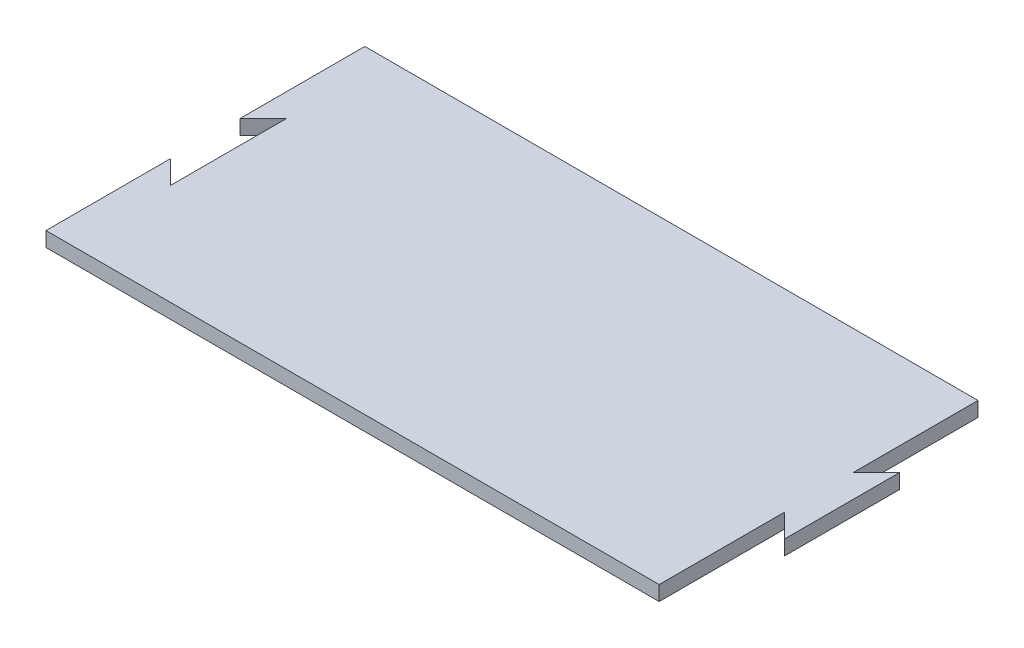
SolidWorks part; units mm, degrees
ref_plane "Front Plane" through (0, 0, 0) normal (0, 0, 1) x (1, 0, 0)
ref_plane "Top Plane" through (0, 0, 0) normal (0, 1, 0) x (1, 0, 0)
ref_plane "Right Plane" through (0, 0, 0) normal (1, 0, 0) x (0, 0, -1)
other "Default"
sketch "Sketch1" plane through (0, 0, 0) normal (0, 1, 0) x (1, 0, 0)
  line L0 (-354.15, 75) -> (-354.15, -75)
  line L1 (-354.15, -75) -> (-260.5, -75)
  line L2 (-260.5, -75) -> (-260.5, -68.65)
  line L3 (-260.5, -68.65) -> (260.5, -68.65)
  line L4 (260.5, -68.65) -> (260.5, -75)
  line L5 (260.5, -75) -> (354.15, -75)
  line L6 (354.15, -75) -> (354.15, 75)
  line L7 (354.15, 75) -> (260.5, 75)
  line L8 (260.5, 75) -> (260.5, 68.65)
  line L9 (260.5, 68.65) -> (-260.5, 68.65)
  line L10 (-260.5, 68.65) -> (-260.5, 75)
  line L11 (-260.5, 75) -> (-354.15, 75)
  point P11 (0, -68.65)
  point P13 (354.15, 0)
  dimension "D1" = 150
  dimension "D2" = 6.35
  dimension "TabWidth" = 93.65
  dimension "Width" = 708.3
extrude "Boss-Extrude1" add sketch "Sketch1" along normal mid plane 6.35
sketch "Sketch2" [suppressed] plane through (0, 3.175, 0) normal (0, 1, 0) x (1, 0, 0)
  line L0 (233.15, -86.7757) -> (233.15, 92.4765) construction
  line L5 (239.5, 75) -> (139.5, 75) construction
  line L6 (43.15, -11.35) -> (183.15, -11.35)
  line L7 (188.15, 88.359) -> (188.15, -110.3451) construction
  line L8 (-49.46, 51.57) -> (-49.46, 61.57) construction
  line L13 (239.5, -75) -> (239.5, 75) construction
  line L14 (38.15, -90.5492) -> (38.15, 114.8099) construction
  line L23 (139.5, 68.65) -> (-139.5, 68.65) construction
  line L24 (-80.91, -8.28) -> (18.15, -8.28) construction
  line L25 (-80.91, -8.28) -> (-80.91, 66.65) construction
  line L26 (-80.91, 66.65) -> (18.15, 66.65) construction
  line L27 (18.15, -8.28) -> (18.15, 66.65) construction
  line L28 (-80.91, -8.28) -> (18.15, 66.65) construction
  line L29 (-80.91, 66.65) -> (18.15, -8.28) construction
  line L30 (-75.83, -3.2) -> (13.07, -3.2) construction
  line L31 (-75.83, -3.2) -> (-75.83, 61.57) construction
  line L32 (-75.83, 61.57) -> (13.07, 61.57) construction
  line L33 (13.07, -3.2) -> (13.07, 61.57) construction
  line L34 (-75.83, -3.2) -> (13.07, 61.57) construction
  line L35 (-75.83, 61.57) -> (13.07, -3.2) construction
  line L36 (-155.36, 15.85) -> (-110.91, 15.85) construction
  line L37 (-155.36, 15.85) -> (-155.36, 66.65) construction
  line L38 (-155.36, 66.65) -> (-110.91, 66.65) construction
  line L39 (-110.91, 15.85) -> (-110.91, 66.65) construction
  line L40 (-155.36, 15.85) -> (-110.91, 66.65) construction
  line L41 (-155.36, 66.65) -> (-110.91, 15.85) construction
  line L42 (-151.55, 19.66) -> (-114.72, 19.66) construction
  line L43 (-151.55, 19.66) -> (-151.55, 62.84) construction
  line L44 (-151.55, 62.84) -> (-114.72, 62.84) construction
  line L45 (-114.72, 19.66) -> (-114.72, 62.84) construction
  line L46 (-151.55, 19.66) -> (-114.72, 62.84) construction
  line L47 (-151.55, 62.84) -> (-114.72, 19.66) construction
  line L48 (-51.46, 51.57) -> (-51.46, 61.57)
  line L49 (-47.46, 51.57) -> (-47.46, 61.57)
  line L50 (-9.46, 51.57) -> (-9.46, 61.57) construction
  line L51 (-11.46, 51.57) -> (-11.46, 61.57)
  line L52 (-7.46, 51.57) -> (-7.46, 61.57)
  line L53 (43.15, -11.35) -> (43.15, 63.65)
  line L54 (43.15, 63.65) -> (183.15, 63.65)
  line L55 (183.15, -11.35) -> (183.15, 63.65)
  line L56 (43.15, -11.35) -> (183.15, 63.65) construction
  line L57 (43.15, 63.65) -> (183.15, -11.35) construction
  line L58 (194.5, 75) -> (188.15, 75)
  line L59 (194.5, 75) -> (194.5, 55)
  line L60 (194.5, 55) -> (188.15, 55)
  line L61 (188.15, 75) -> (188.15, 55)
  line L62 (31.8, -31.35) -> (194.5, -31.35) construction
  line L63 (194.5, -37.7) -> (188.15, -37.7)
  line L64 (194.5, -37.7) -> (194.5, -17.7)
  line L65 (194.5, -17.7) -> (188.15, -17.7)
  line L66 (188.15, -37.7) -> (188.15, -17.7)
  line L67 (38.15, -37.7) -> (31.8, -37.7)
  line L68 (38.15, -37.7) -> (38.15, -17.7)
  line L69 (38.15, -17.7) -> (31.8, -17.7)
  line L70 (31.8, -37.7) -> (31.8, -17.7)
  line L71 (38.15, 55) -> (31.8, 55)
  line L72 (38.15, 55) -> (38.15, 75)
  line L73 (38.15, 75) -> (31.8, 75)
  line L74 (31.8, 55) -> (31.8, 75)
  line L76 (103.15, -31.35) -> (123.15, -31.35)
  line L77 (103.15, -31.35) -> (103.15, -37.7)
  line L78 (103.15, -37.7) -> (123.15, -37.7)
  line L79 (123.15, -31.35) -> (123.15, -37.7)
  circle A0 centre (-75.83, 61.57) radius 1.375
  circle A1 centre (13.07, 61.57) radius 1.375
  circle A2 centre (13.07, -3.2) radius 1.375
  circle A3 centre (-75.83, -3.2) radius 1.375
  circle A4 centre (-42.81, -3.2) radius 1.375
  circle A6 centre (-114.72, 19.66) radius 1.375
  circle A7 centre (-151.55, 19.66) radius 1.375
  circle A8 centre (-151.55, 62.84) radius 1.375
  circle A9 centre (-114.72, 63.48) radius 1.375
  arc A10 (-51.46, 51.57) -> (-47.46, 51.57) centre (-49.46, 51.57) ccw
  arc A11 (-47.46, 61.57) -> (-51.46, 61.57) centre (-49.46, 61.57) ccw
  arc A12 (-11.46, 51.57) -> (-7.46, 51.57) centre (-9.46, 51.57) ccw
  arc A13 (-7.46, 61.57) -> (-11.46, 61.57) centre (-9.46, 61.57) ccw
  point P0 (113.15, 26.15)
  point P28 (-31.38, 29.185)
  point P33 (-31.38, 29.185)
  point P44 (-133.135, 41.25)
  point P49 (-133.135, 41.25)
  point P60 (-49.46, 56.57)
  point P67 (-9.46, 56.57)
  point P85 (113.15, -31.35)
  dimension "D17" = 2.75
  dimension "D25" = 0.64
  dimension "D27" = 2
  dimension "D4" = 6.35
  dimension "D5" = 5
  dimension "D7" = 5
  dimension "D8" = 75
  dimension "D9" = 150
  dimension "D10" = 6.35
  dimension "D12" = 45
  dimension "D13" = 99.06
  dimension "D14" = 74.93
  dimension "D15" = 88.9
  dimension "D16" = 64.77
  dimension "D18" = 2
  dimension "D19" = 20
  dimension "D20" = 33.02
  dimension "D21" = 50.8
  dimension "D22" = 44.45
  dimension "D23" = 36.83
  dimension "D24" = 43.18
  dimension "D26" = 30
  dimension "D28" = 26.37
  dimension "D29" = 22.53
  dimension "D30" = 10
  dimension "D6" = 5
  dimension "D31" = 100
  dimension "D32" = 20
extrude "Back Only" [suppressed] cut sketch "Sketch2" against normal through all
sketch "Sketch3" [suppressed] plane through (0, 3.175, 0) normal (0, 1, 0) x (1, 0, 0)
  line L0 (-225.15, 9.65) -> (-200.15, 9.65) construction
  line L1 (-230.15, -0.35) -> (-195.15, -0.35) construction
  line L2 (-230.15, -0.35) -> (-230.15, 19.65) construction
  line L3 (-230.15, 19.65) -> (-195.15, 19.65) construction
  line L4 (-195.15, -0.35) -> (-195.15, 19.65) construction
  line L5 (-230.15, -0.35) -> (-195.15, 19.65) construction
  line L6 (-230.15, 19.65) -> (-195.15, -0.35) construction
  line L9 (-233.15, -93.1255) -> (-233.15, 99.5323) construction
  line L10 (-239.5, 75) -> (-239.5, -75) construction
  line L11 (139.5, 68.65) -> (38.15, 68.65) construction
  line L12 (0, -88.5309) -> (0, 117.3513) construction
  circle A1 centre (-200.15, 9.65) radius 2.5
  circle A2 centre (-225.15, 9.65) radius 2.5
  circle A3 centre (200.15, 9.65) radius 2.5
  circle A5 centre (225.15, 9.65) radius 2.5
  point P0 (-212.65, 9.65)
  dimension "D4" = 5
  dimension "D1" = 35
  dimension "D2" = 20
  dimension "D5" = 25
  dimension "D6" = 59
  dimension "D7" = 6.35
  dimension "D8" = 3
extrude "Front and Back" [suppressed] cut sketch "Sketch3" against normal through all
sketch "Sketch4" plane through (0, -3.175, 0) normal (0, -1, 0) x (1, 0, 0)
  line L0 (-329.1, -3.15) -> (-323.1, -3.15) construction
  line L1 (202.9, -3.15) -> (208.9, -3.15) construction
  line L2 (-329.1, -3.15) -> (-323.1, -3.15) construction
  line L3 (202.9, -3.15) -> (208.9, -3.15) construction
  line L4 (-184.15, -68.65) -> (-184.15, -15)
  line L5 (260.5, -68.65) -> (-260.5, -68.65) construction
  line L6 (-184.15, -15) -> (-174.15, -25)
  line L7 (-174.15, -25) -> (-174.15, 25)
  line L8 (-174.15, 25) -> (-184.15, 15)
  line L9 (-184.15, 15) -> (-184.15, 68.65)
  line L10 (-260.5, 68.65) -> (260.5, 68.65) construction
  line L11 (-184.25, -68.65) -> (-184.25, -14.7586)
  line L12 (-184.25, -14.7586) -> (-174.25, -24.7586)
  line L13 (-174.25, -24.7586) -> (-174.25, 24.7586)
  line L14 (-174.25, 24.7586) -> (-184.25, 14.7586)
  line L15 (-184.25, 14.7586) -> (-184.25, 68.65)
  line L16 (-184.25, -68.65) -> (-184.15, -68.65)
  line L17 (-184.25, 68.65) -> (-184.15, 68.65)
  line L18 (80, -68.65) -> (80, -15)
  line L19 (80, -15) -> (90, -25)
  line L20 (90, -25) -> (90, 25)
  line L21 (90, 25) -> (80, 15)
  line L22 (80, 15) -> (80, 68.65)
  line L23 (79.9, -68.65) -> (79.9, -14.7586)
  line L24 (79.9, -14.7586) -> (89.9, -24.7586)
  line L25 (89.9, -24.7586) -> (89.9, 24.7586)
  line L26 (89.9, 24.7586) -> (79.9, 14.7586)
  line L27 (79.9, 14.7586) -> (79.9, 68.65)
  line L28 (79.9, -68.65) -> (80, -68.65)
  line L29 (79.9, 68.65) -> (80, 68.65)
  line L30 (-174.15, 0) -> (-354.15, 0) construction
  line L31 (-354.15, -75) -> (-354.15, 75) construction
  line L32 (-184.25, 0) -> (90, 0) construction
  line L33 (79.9, 0) -> (354.15, 0) construction
  line L34 (354.15, 75) -> (354.15, -75) construction
  circle A0 centre (-326.1, 14.85) radius 4
  circle A1 centre (205.9, 14.85) radius 4
  point P8 (205.9, -3.15)
  point P10 (-326.1, -3.15)
  point P14 (-174.15, 0)
  dimension "D1" = 8
  dimension "D2" = 18
  dimension "D3" = 50
  dimension "D4" = 10
  dimension "D7" = 180
  dimension "D5" = 0.1
  dimension "D6" = 2
extrude "Left and Right" cut sketch "Sketch4" against normal through all
sketch "Sketch5" [suppressed] plane through (0, 3.175, 0) normal (0, 1, 0) x (1, 0, 0)
  line L0 (260.5, 68.65) -> (80, 68.65) construction
  line L1 (-155.15, -23.35) -> (-53.15, -23.35) construction
  line L2 (-155.15, -23.35) -> (-155.15, 58.65) construction
  line L3 (-155.15, 58.65) -> (-53.15, 58.65) construction
  line L4 (-53.15, -23.35) -> (-53.15, 58.65) construction
  line L5 (-155.15, -23.35) -> (-53.15, 58.65) construction
  line L6 (-155.15, 58.65) -> (-53.15, -23.35) construction
  line L7 (-354.15, 75) -> (-354.15, -75) construction
  line L9 (-150.65, -28.85) -> (-57.65, -28.85)
  line L10 (-150.65, -28.85) -> (-150.65, 64.15)
  line L11 (-150.65, 64.15) -> (-57.65, 64.15)
  line L12 (-57.65, -28.85) -> (-57.65, 64.15)
  line L13 (-150.65, -28.85) -> (-57.65, 64.15) construction
  line L14 (-150.65, 64.15) -> (-57.65, -28.85) construction
  circle A0 centre (-155.15, 58.65) radius 2.5
  circle A1 centre (-53.15, 58.65) radius 2.5
  circle A2 centre (-53.15, -23.35) radius 2.5
  circle A3 centre (-155.15, -23.35) radius 2.5
  point P0 (-104.15, 17.65)
  point P13 (-104.15, 17.65)
  dimension "D3" = 5
  dimension "D1" = 102
  dimension "D2" = 82
  dimension "D4" = 10
  dimension "D5" = 250
  dimension "D6" = 93
extrude "Right Only" [suppressed] cut sketch "Sketch5" against normal through all
fillet "Right Only 2" [suppressed] radius 5
delete or keep bodies "Body-Delete/Keep 1" [suppressed] type keep bodies bodies 107
delete or keep bodies "Body-Delete/Keep 2" type keep bodies bodies 108
delete or keep bodies "Body-Delete/Keep 3" [suppressed] type keep bodies bodies 109
delete or keep bodies "Body-Delete/Keep 4" [suppressed] type keep bodies bodies 107
delete or keep bodies "Body-Delete/Keep 5" [suppressed] type keep bodies bodies 109
delete or keep bodies "Body-Delete/Keep 6" [suppressed] type keep bodies bodies 105
